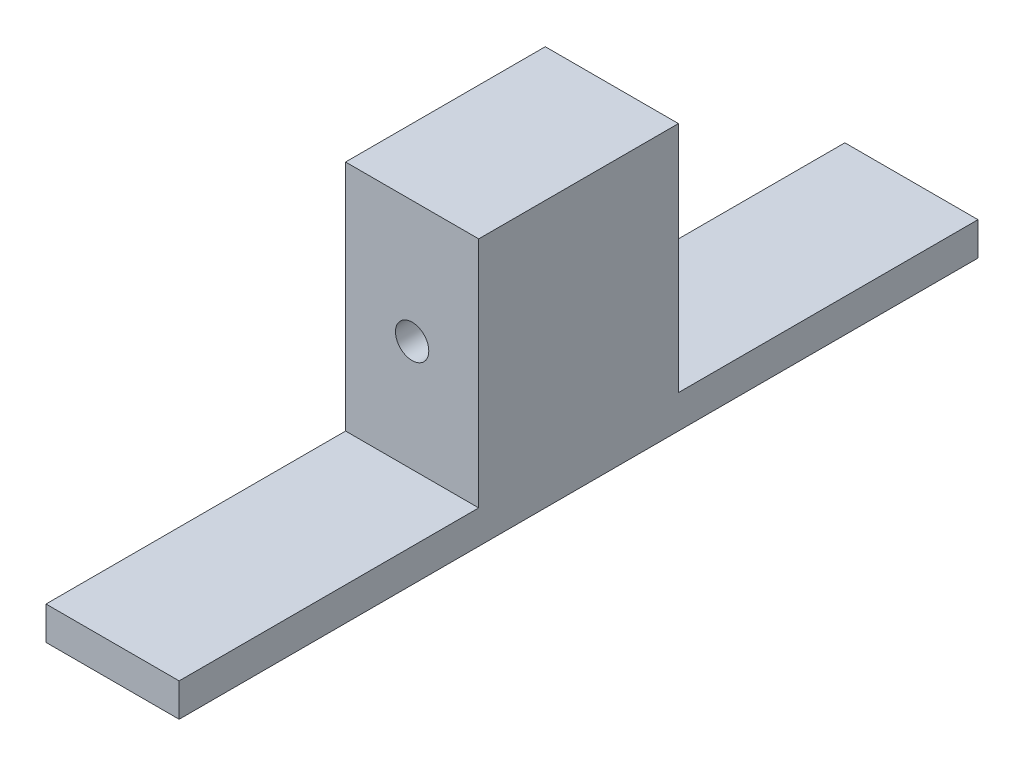
SolidWorks part; units mm, degrees
ref_plane "Front Plane" through (0, 0, 0) normal (0, 0, 1) x (1, 0, 0)
ref_plane "Top Plane" through (0, 0, 0) normal (0, 1, 0) x (1, 0, 0)
ref_plane "Right Plane" through (0, 0, 0) normal (1, 0, 0) x (0, 0, -1)
sketch "Sketch-Profile" plane through (0, 0, 0) normal (1, 0, 0) x (0, 0, -1)
  line L0 (-76.2, 6.35) -> (-76.2, 0)
  line L5 (-76.2, 6.35) -> (-19.05, 6.35)
  line L6 (-76.2, 0) -> (76.2, 0)
  line L7 (76.2, 6.35) -> (76.2, 0)
  line L8 (-76.2, 6.35) -> (76.2, 0) construction
  line L9 (-76.2, 0) -> (76.2, 6.35) construction
  line L10 (-19.05, 50.8) -> (-19.05, 6.35)
  line L11 (-19.05, 50.8) -> (19.05, 50.8)
  line L13 (19.05, 50.8) -> (19.05, 6.35)
  line L14 (-19.05, 50.8) -> (19.05, 6.35) construction
  line L15 (-19.05, 6.35) -> (19.05, 50.8) construction
  line L16 (19.05, 6.35) -> (76.2, 6.35)
  point P1 (0, 3.175)
  point P2 (0, 28.575)
  dimension "D1" = 6.35
  dimension "D2" = 50.8
  dimension "D3" = 152.4
  dimension "D4" = 38.1
extrude "Boss-Extrude1" add sketch "Sketch-Profile" along normal blind 25.4
sketch "Sketch-Hole Location" plane through (0, 0, 19.05) normal (0, 0, 1) x (1, 0, 0)
  line L0 (12.7, 0) -> (12.7, 50.8) construction
  line L1 (25.4, 0) -> (0, 0) construction
  line L2 (25.4, 50.8) -> (0, 50.8) construction
  line L3 (103.6069, 27.5181) -> (17.1719, 27.5181) construction
  point P6 (12.7, 27.5181)
sketch "Sketch5" plane through (0, 0, 19.05) normal (0, 0, 1) x (1, 0, 0)
  point P0 (12.7, 27.5181)
hole_wizard "1/4 (0.25) Diameter Hole1" positions "Sketch5" profile "Sketch4" hole size "1/4" standard "ANSI Inch" end condition through all
sketch "Sketch4" plane through (12.7, 27.5181, 19.05) normal (1, 0, 0) x (0, -1, 0)
  line L0 (0, 0) -> (0, 95.25)
  line L1 (0, 95.25) -> (3.175, 95.25)
  line L2 (3.175, 95.25) -> (3.175, 0)
  line L5 (3.175, 0) -> (0, 0)
  line L11 (0, -6.35) -> (0, 107.95) construction
  dimension "Thru Hole Dia." = 6.35
  dimension "Thru Hole Depth" = 95.25
